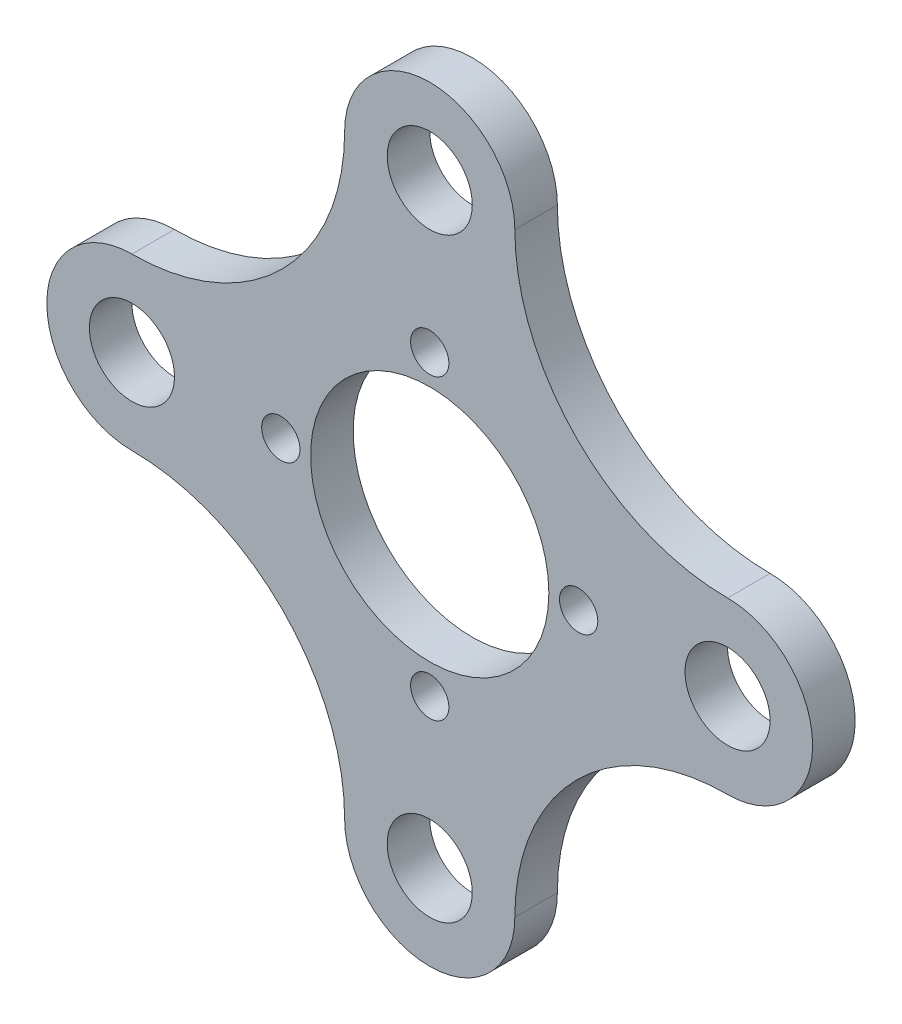
SolidWorks part; units mm, degrees
material "3.1325 (EN-AW 2017A)"
ref_plane "Płaszczyzna przednia" through (0, 0, 0) normal (0, 0, 1) x (1, 0, 0)
ref_plane "Płaszczyzna górna" through (0, 0, 0) normal (0, 1, 0) x (1, 0, 0)
ref_plane "Płaszczyzna prawa" through (0, 0, 0) normal (1, 0, 0) x (0, 0, -1)
sketch "Szkic1" plane through (0, 0, 0) normal (0, 0, 1) x (1, 0, 0)
  line L0 (0, 14) -> (0, 17.5)
  line L1 (14, 0) -> (17.5, 0)
  arc A0 (-17.3554, 2.2453) -> (-17.3554, -2.2453) centre (0, 0) ccw
  circle A1 centre (0, 17.5) radius 2.25
  circle A2 centre (17.5, 0) radius 2.25
  circle A3 centre (0, -17.5) radius 2.25
  circle A4 centre (-17.5, 0) radius 2.25
  circle A5 centre (0, 0) radius 14
  circle A6 centre (0, 0) radius 24
  arc A7 (2.2453, 17.3554) -> (-2.2453, 17.3554) centre (0, 0) ccw
  arc A8 (17.3554, -2.2453) -> (17.3554, 2.2453) centre (0, 0) ccw
  arc A9 (-2.2453, -17.3554) -> (2.2453, -17.3554) centre (0, 0) ccw
  circle A10 centre (0, 0) radius 17.5
  dimension "D1" = 28
  dimension "D2" = 35
  dimension "D3" = 48
  dimension "D4" = 4.5
extrude "Dodanie-wyciągnięcie1" add sketch "Szkic1" along normal blind 5 contours A1 A10 A4 A3 A2 L1 A5 L0 | A2 A10 A1 L0 A5 L1 | A6 A10 A2 A3 A4 A1 region at (-10.2466, -10.2466, 0) region at (10.1996, 10.1996, 0) region at (-23.3212, 0, 0)
sketch "Szkic2" plane through (0, 0, 5) normal (0, 0, 1) x (1, 0, 0)
  line L0 (-10, -35) -> (-10, -20.1556)
  line L5 (35, 0) -> (35, -10)
  line L6 (35, -10) -> (20.1556, -10)
  line L7 (10, -35) -> (10, -20.1556)
  line L8 (-35, -10) -> (-20.1556, -10)
  line L9 (-10, 35) -> (-10, 20.1556)
  line L10 (-35, 10) -> (-20.1556, 10)
  line L11 (10, 20.1556) -> (10, 35)
  line L12 (20.1556, 10) -> (35, 10)
  circle A0 centre (0, 0) radius 22.5
  circle A1 centre (0, 35) radius 5
  circle A2 centre (0, 35) radius 10
  circle A3 centre (35, 0) radius 5
  circle A4 centre (35, 0) radius 10
  circle A5 centre (0, -35) radius 5
  circle A6 centre (0, -35) radius 10
  circle A7 centre (-35, 0) radius 5
  circle A8 centre (-35, 0) radius 10
  arc A9 (-35, -10) -> (-10, -35) centre (-35, -35) cw
  arc A10 (10, -35) -> (35, -10) centre (35, -35) cw
  arc A11 (35, 10) -> (10, 35) centre (35, 35) cw
  arc A12 (-10, 35) -> (-35, 10) centre (-35, 35) cw
  circle A13 centre (0, 0) radius 35
  circle M10 centre (0, 17.5) radius 2.25
  circle M11 centre (-17.5, 0) radius 2.25
  circle M12 centre (0, -17.5) radius 2.25
  circle M13 centre (17.5, 0) radius 2.25
  circle M14 centre (0, 0) radius 14
  circle M15 centre (0, 0) radius 24
  dimension "D2" = 20
  dimension "D3" = 45
  dimension "D7" = 10
  dimension "D1" = 35
extrude "Dodanie-wyciągnięcie2" add sketch "Szkic2" against normal blind 5 contours A13 A8 A7 | A8 A13 A7 | L10 A13 A8 L8 M15 | L9 A13 A12 L10 M15 | L11 A13 A2 L9 M15 | A2 A13 A1 | A13 A2 A1 | A13 A6 A5 | A13 A3 L5 A4 | A3 A13 A4 | A4 A13 L12 L6 M15 | L12 A13 A11 L11 M15 | L7 A13 A10 L6 M15 | A6 A13 A5 | L8 A13 A9 L0 M15 | L0 A13 A6 L7 M15 | A0 L8 L0 M15 | A0 L0 L7 M15 | A0 M11 M13 M14 M12 M10 | A0 L7 L6 M15 | A0 L6 L12 M15 | A0 L12 L11 M15 | A0 L11 L9 M15 | A0 L9 L10 M15 | A0 L10 L8 M15 | A13 A4 L5 A3 | A13 L6 A4 | A13 A10 L6 | A13 A4 L12 | A13 L12 A11 | A13 A11 L11 | A13 L11 A2 | A13 L9 A12 | A13 A2 L9 | A13 L10 A8 | A13 A12 L10 | A13 A8 L8 | A13 L8 A9 | A13 L0 A6 | A13 A9 L0 | A13 A6 L7 | A13 L7 A10 | A8 | A7 region at (-10.013, -33.9009, 5) region at (-9.7446, -34.3004, 5) region at (-9.9692, -33.9168, 5) region at (-10.0122, -33.5026, 5) region at (-9.768, -27.6792, 5) region at (9.9692, -33.9168, 5) region at (10.013, -33.9009, 5) region at (0, -29.7069, 5) region at (-16.1364, -16.1364, 5) region at (-9.7963, -20.9865, 5) region at (10.3329, -27.6792, 5) region at (-33.9009, -10.013, 5) region at (-15.4599, -15.4599, 5) region at (-23.7963, 0, 5) region at (-27.6792, -9.768, 5) region at (16.1364, -16.1364, 5) region at (33.9009, -10.013, 5) region at (-33.9168, -9.9692, 5) region at (-44.7696, 0, 5) region at (-16.1364, 16.1364, 5) region at (-27.6792, 10.3329, 5) region at (23.6747, -5.1672, 5) region at (20.9865, -9.7963, 5) region at (34.5248, -8.0175, 5) region at (35.2304, -7.5, 5) region at (33.9168, -9.9692, 5) region at (-33.9009, 10.013, 5) region at (-33.9168, 9.9692, 5) region at (-29.7069, 0, 5) region at (0, 23.7963, 5) region at (-9.768, 27.6792, 5) region at (29.7069, 0, 5) region at (-10.013, 33.9009, 5) region at (-9.9692, 33.9168, 5) region at (16.1364, 16.1364, 5) region at (10.3329, 27.6792, 5) region at (33.9168, 9.9692, 5) region at (33.9009, 10.013, 5) region at (0, 44.7696, 5) region at (0, 29.7069, 5) region at (9.9692, 33.9168, 5) region at (10.013, 33.9009, 5)
